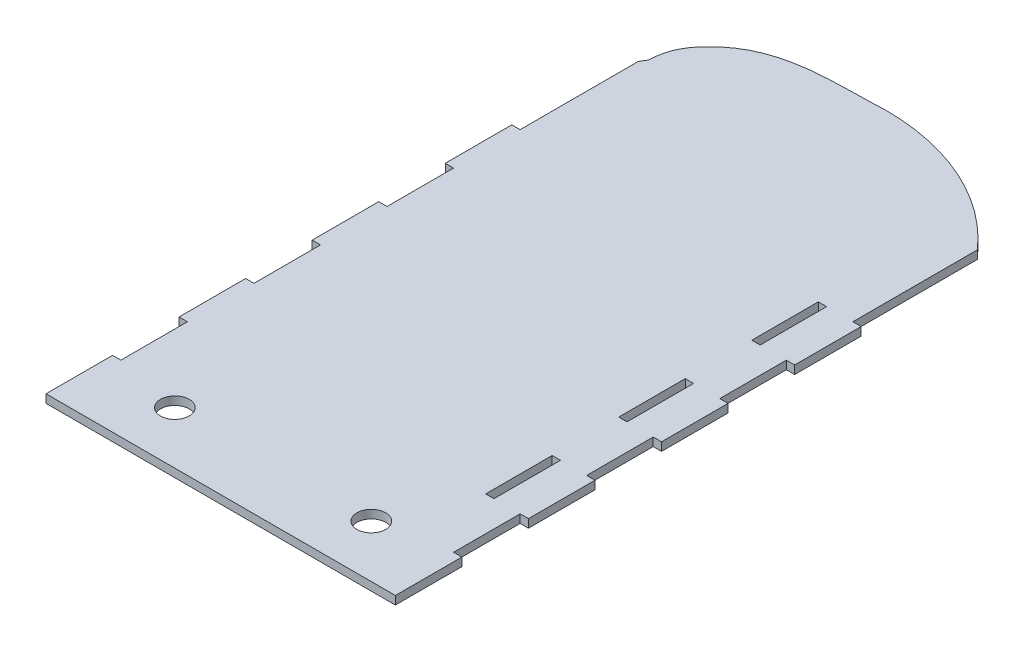
SolidWorks part; units mm, degrees
ref_plane "Front Plane" through (0, 0, 0) normal (0, 0, 1) x (1, 0, 0)
ref_plane "Top Plane" through (0, 0, 0) normal (0, 1, 0) x (1, 0, 0)
ref_plane "Right Plane" through (0, 0, 0) normal (1, 0, 0) x (0, 0, -1)
sketch "Sketch2" plane through (0, 0, 0) normal (0, 1, 0) x (1, 0, 0)
  line L0 (127, 0) -> (127, 40) construction
  line L1 (0, 0) -> (254, 0)
  line L2 (0, 0) -> (0, 508)
  line L3 (0, 508) -> (254, 508)
  line L4 (254, 0) -> (254, 508)
  line L5 (112, 0) -> (112, 40) construction
  circle A0 centre (52, 40) radius 11
  circle A1 centre (202, 40) radius 11
  point P11 (0, 0)
  point P12 (127, 40)
  dimension "D3" = 22
  dimension "D1" = 508
  dimension "D2" = 254
  dimension "D4" = 40
  dimension "D5" = 15
  dimension "D6" = 60
extrude "Boss-Extrude1" add sketch "Sketch2" along normal blind 6.35
sketch "Sketch3" plane through (0, 6.35, 0) normal (0, 1, 0) x (1, 0, 0)
  line L0 (127, 508) -> (127, 338.6667) construction
  line L1 (254, 508) -> (0, 508) construction
  line L2 (127, 338.6667) -> (127, 169.3333) construction
  line L3 (127, 169.3333) -> (127, 0) construction
  line L4 (0, 0) -> (254, 0) construction
  line L5 (254, 0) -> (254, 508) construction
  line L6 (254, 508) -> (127, 508)
  line L7 (254, 450.6701) -> (254, 508)
  arc A1 (127, 508) -> (254, 450.6701) centre (127, 338.6667) cw
extrude "Cut-Extrude1" cut sketch "Sketch3" against normal up to next
sketch "Sketch5" plane through (0, 6.35, 0) normal (0, 1, 0) x (1, 0, 0)
  line L0 (254, 450.6701) -> (0, 450.6701) construction
  line L1 (0, 508) -> (0, 0) construction
  line L2 (3, 450.6701) -> (0, 445.8071)
  line L3 (0, 508) -> (0, 445.8071)
  line L6 (0, 508) -> (0, 526.7662)
  line L7 (0, 526.7662) -> (127, 526.7662)
  line L8 (127, 508) -> (127, 526.7662)
  circle A0 centre (45, 450.6701) radius 22 construction
  arc A2 (16.9934, 481.9692) -> (3, 450.6701) centre (45, 450.6701) ccw
  circle A3 centre (45, 450.6701) radius 42 construction
  spline S0 degree 3 poles (16.9934, 481.9692) (44.7711, 511.7661) (91.2093, 505.8566) (127, 508) knots 0 0 0 0 1 1 1 1
  dimension "D1" = 44
  dimension "D3" = 45
  dimension "D2" = 20
extrude "Cut-Extrude2" cut sketch "Sketch5" against normal up to next
sketch "Sketch7" plane through (0, 0, 0) normal (0, -1, 0) x (1, 0, 0)
  line L1 (254, 0) -> (260.35, 0)
  line L2 (254, 0) -> (254, -50.8)
  line L3 (254, -50.8) -> (260.35, -50.8)
  line L4 (260.35, 0) -> (260.35, -50.8)
  line L5 (0, 0) -> (-6.35, 0)
  line L6 (0, 0) -> (0, -50.8)
  line L7 (0, -50.8) -> (-6.35, -50.8)
  line L8 (-6.35, 0) -> (-6.35, -50.8)
  dimension "D1" = 6.35
  dimension "D2" = 50.8
  dimension "D3" = 6.35
  dimension "D4" = 50.8
extrude "Boss-Extrude2" add sketch "Sketch7" against normal up to surface (6.35 mm away) up to face at (86.1173, 6.35, -334.1803)
pattern_linear "LPattern1" count 4 spacing 101.6 along (0, 0, -1) of "Boss-Extrude2"
sketch "Sketch8" plane through (0, 6.35, 0) normal (0, 1, 0) x (1, 0, 0)
  line L0 (254, 152.4) -> (254, 203.2) construction
  line L5 (234, 152.4) -> (227.65, 152.4)
  line L7 (234, 152.4) -> (234, 101.6)
  line L9 (234, 101.6) -> (227.65, 101.6)
  line L10 (227.65, 152.4) -> (227.65, 101.6)
  line L11 (254, 101.6) -> (260.35, 101.6) construction
  line L12 (260.35, 101.6) -> (260.35, 152.4) construction
  point P10 (227.65, 157.4226)
  dimension "D1" = 20
extrude "Cut-Extrude3" cut sketch "Sketch8" against normal up to next
pattern_linear "LPattern2" count 3 spacing 101.6 along (0, 0, -1) of "Cut-Extrude3"
